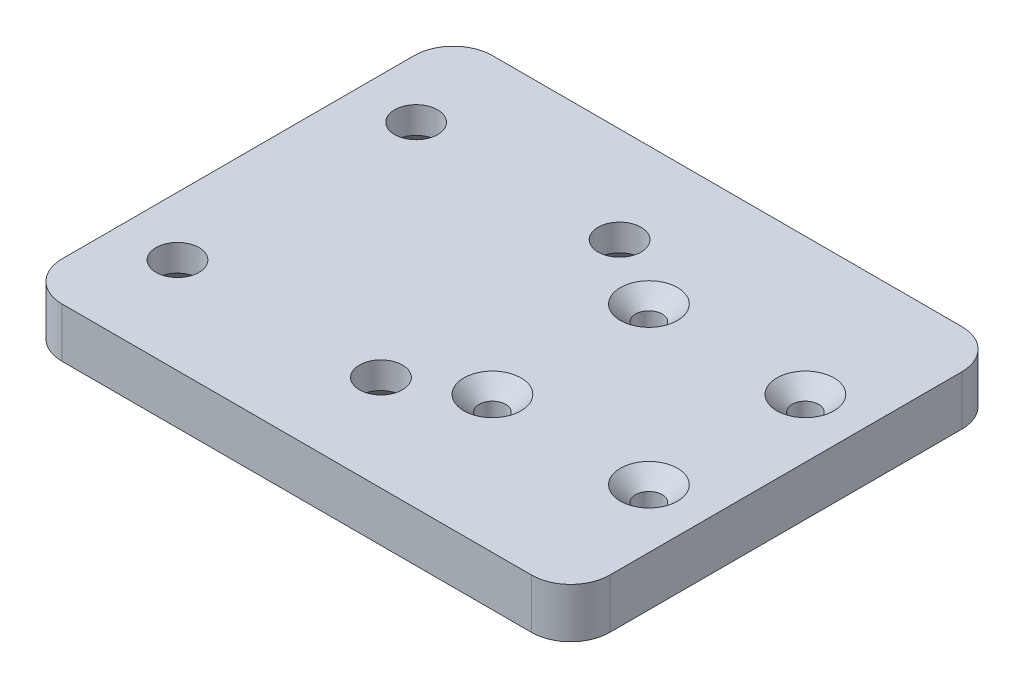
SolidWorks part; units mm, degrees
material "6061-T6 (SS)"
ref_plane "Front Plane" through (0, 0, 0) normal (0, 0, 1) x (1, 0, 0)
ref_plane "Top Plane" through (0, 0, 0) normal (0, 1, 0) x (1, 0, 0)
ref_plane "Right Plane" through (0, 0, 0) normal (1, 0, 0) x (0, 0, -1)
sketch "Sketch1" plane through (0, 0, 0) normal (0, 1, 0) x (1, 0, 0)
  line L0 (-11.7884, -21) -> (-11.7884, 21) construction
  line L1 (37.7116, -27.5) -> (-32.2884, -27.5)
  line L2 (37.7116, -27.5) -> (37.7116, 27.5)
  line L3 (37.7116, 27.5) -> (-32.2884, 27.5)
  line L4 (-32.2884, -27.5) -> (-32.2884, 27.5)
  line L5 (6.2116, 0) -> (-29.7884, 0) construction
  line L6 (6.2116, -21) -> (-29.7884, -21)
  line L7 (6.2116, -21) -> (6.2116, 21)
  line L8 (6.2116, 21) -> (-29.7884, 21)
  line L9 (-29.7884, -21) -> (-29.7884, 21)
  line L10 (20.2116, -24) -> (20.2116, 24) construction
  line L11 (33.7116, 0) -> (6.7116, 0) construction
  line L12 (33.7116, -24) -> (6.7116, -24)
  line L13 (33.7116, -24) -> (33.7116, 24)
  line L14 (33.7116, 24) -> (6.7116, 24)
  line L15 (6.7116, -24) -> (6.7116, 24)
  line L16 (37.7116, 0) -> (-32.2884, 0) construction
  circle A0 centre (30.2116, -10) radius 1
  circle A1 centre (10.2116, -10) radius 1
  circle A2 centre (30.2116, 10) radius 1
  circle A3 centre (10.2116, 10) radius 1
  circle A4 centre (1.2116, -15.25) radius 1
  circle A5 centre (-24.7884, -15.25) radius 1
  circle A6 centre (1.2116, 15.25) radius 1
  circle A7 centre (-24.7884, 15.25) radius 1
  dimension "D3" = 20
  dimension "D9" = 55
  dimension "D11" = 7.5
  dimension "D1" = 26
  dimension "D2" = 30.5
  dimension "D4" = 20
  dimension "D5" = 48
  dimension "D6" = 27
  dimension "D7" = 36
  dimension "D8" = 42
  dimension "D10" = 70
  dimension "D12" = 7.5
extrude "Boss-Extrude1" add sketch "Sketch1" along normal blind 6.35 contours L4 L3 L2 L1
extrude "Cut-Extrude1" cut sketch "Sketch1<3>" against normal up to surface from surface contours A0 | A2 | A1 | A3 | A6 | A4 | A5 | A7 up to face at (2.7116, 0, 0) starting at face at (2.7116, 6.35, 0)
sketch "Sketch1<3>" plane through (0, 0, 0) normal (0, 1, 0) x (1, 0, 0) same geometry as "Sketch1"
hole_wizard "CSK for M3 Flat Head Machine Screw1" positions "Sketch2" profile "Sketch3" countersink size "M3" standard "ANSI Metric" end condition through all
sketch "Sketch2" plane through (0, 6.35, 0) normal (0, 1, 0) x (1, 0, 0)
  point P0 (30.2116, -10)
  point P3 (10.2116, -10)
  point P6 (10.2116, 10)
  point P9 (30.2116, 10)
sketch "Sketch3" plane through (30.2116, 6.35, 10) normal (1, 0, 0) x (0, 0, 1)
  line L0 (0, 0) -> (0, 6.35)
  line L1 (0, 6.35) -> (1.7, 6.35)
  line L2 (1.7, 6.35) -> (1.7, 1.95)
  line L3 (1.7, 1.95) -> (3.65, 0)
  line L5 (3.65, 0) -> (0, 0)
  line L6 (-1.7, 1.95) -> (-3.65, 0) construction
  line L11 (0, -6.35) -> (0, 107.95) construction
  dimension "Thru Hole Dia." = 3.4
  dimension "Thru Hole Depth" = 6.35
  dimension "Near C'Sink Dia." = 7.3
  dimension "Near C'Sink Angle" = 90
fillet "Fillet1" radius 5 4 edges at (37.7116, 3.175, 27.5) (-32.2884, 3.175, 27.5) (-32.2884, 3.175, -27.5) (37.7116, 3.175, -27.5)
hole_wizard "CSK for M5 Flat Head Machine Screw2" positions "Sketch9" profile "Sketch10" countersink size "M5" standard "ANSI Metric" end condition through all
sketch "Sketch9" plane through (0, 0, 0) normal (0, -1, 0) x (-1, 0, 0)
  point P0 (24.7884, -15.25)
  point P3 (24.7884, 15.25)
  point P6 (-1.2116, 15.25)
  point P9 (-1.2116, -15.25)
sketch "Sketch10" plane through (-24.7884, 0, 15.25) normal (1, 0, 0) x (0, 0, -1)
  line L0 (0, 0) -> (0, 6.35)
  line L1 (0, 6.35) -> (2.75, 6.35)
  line L2 (2.75, 6.35) -> (2.75, 2.95)
  line L3 (2.75, 2.95) -> (5.7, 0)
  line L5 (5.7, 0) -> (0, 0)
  line L6 (-2.75, 2.95) -> (-5.7, 0) construction
  line L11 (0, -6.35) -> (0, 107.95) construction
  dimension "Thru Hole Dia." = 5.5
  dimension "Thru Hole Depth" = 6.35
  dimension "Near C'Sink Dia." = 11.4
  dimension "Near C'Sink Angle" = 90
